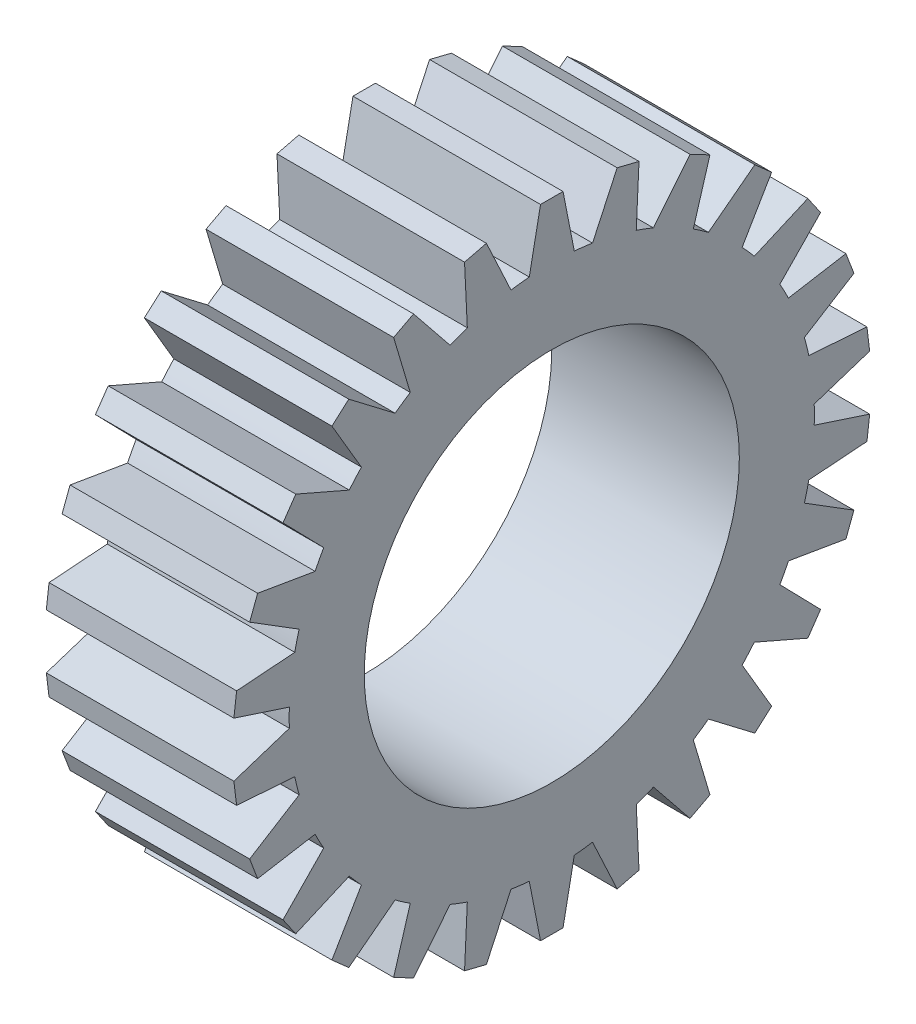
SolidWorks part; units mm, degrees
material "AISI 8620 Steel, carburized"
ref_plane "Front Plane" through (0, 0, 0) normal (1, 0, 0) x (0, 1, 0)
ref_plane "Top Plane" through (0, 0, 0) normal (0, 0, 1) x (0, 1, 0)
ref_plane "Right Plane" through (0, 0, 0) normal (0, 1, 0) x (-1, 0, 0)
sketch "Sketch1" plane through (0, 0, 0) normal (1, 0, 0) x (0, 1, 0)
  line L0 (0, 12.3584) -> (0, -11.8803) construction
  line L1 (-11.4739, 0) -> (21.9917, 0) construction
  line L2 (17, 0.6) -> (17, -0.6)
  line L3 (17, 0.6) -> (13.9485, 1.2)
  line L4 (17, -0.6) -> (13.9485, -1.2)
  circle A0 centre (0, 0) radius 10
  circle A1 centre (0, 0) radius 14
  point P10 (17, 0)
  dimension "D1" = 20
  dimension "D2" = 17
  dimension "D3" = 1.2
  dimension "D4" = 2.4
  dimension "D5" = 4
extrude "Boss-Extrude1" add sketch "Sketch1" along normal mid plane 10 contours A1 A0 region at (0, 13.5915, 0.5836)
extrude "Boss-Extrude2" add sketch "Sketch1<3>" along normal mid plane 10 contours A1 L4 L2 L3 region at (0, 15.3251, 0)
sketch "Sketch1<3>" plane through (0, 0, 0) normal (1, 0, 0) x (0, 1, 0) same geometry as "Sketch1"
pattern_circular "CirPattern1" count 26 over 360 about axis through (5, 0, 0) along (1, 0, 0) of "Boss-Extrude2"
